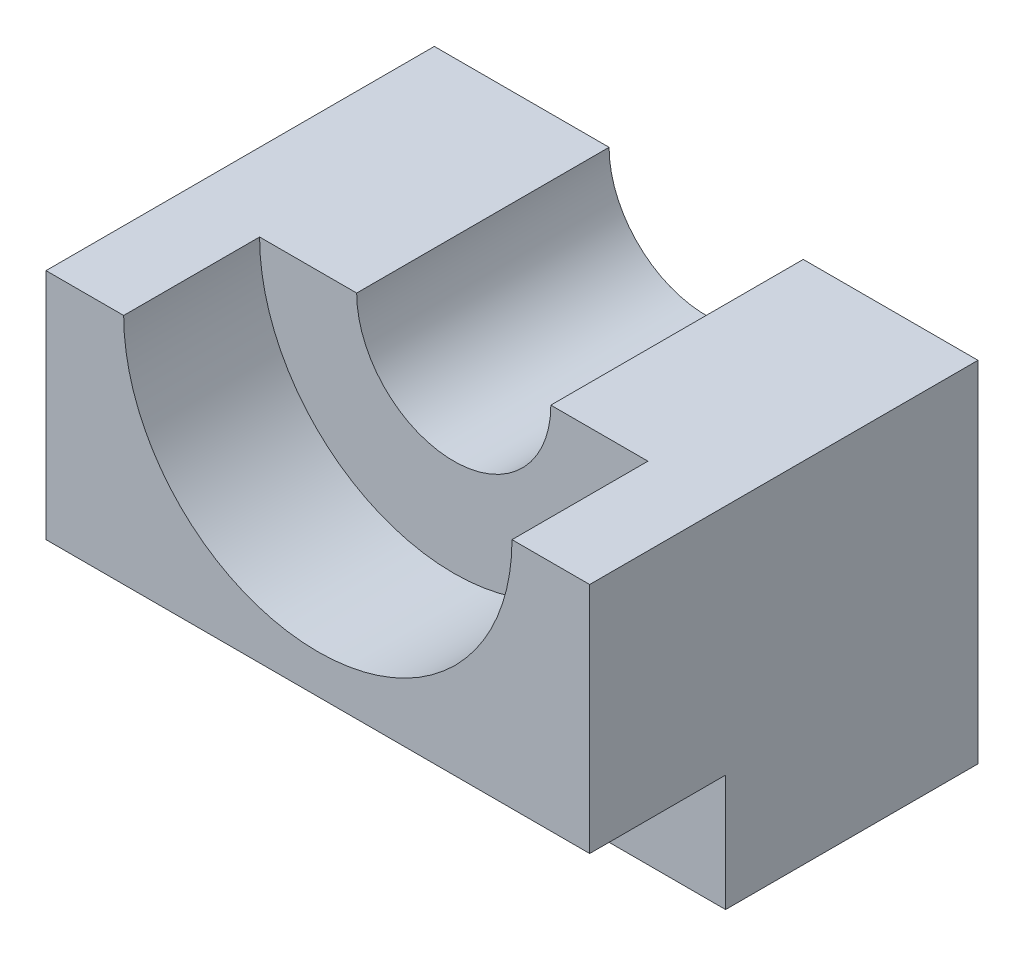
SolidWorks part; units mm, degrees
ref_plane "前视基准面" through (0, 0, 0) normal (0, 0, 1) x (1, 0, 0)
ref_plane "上视基准面" through (0, 0, 0) normal (0, 1, 0) x (1, 0, 0)
ref_plane "右视基准面" through (0, 0, 0) normal (1, 0, 0) x (0, 0, -1)
other "Configuration Table"
sketch "草图5" plane through (0, 0, 0) normal (0, 0, 1) x (1, 0, 0)
  line L0 (5, 9) -> (14, 9)
  line L1 (-14, -9) -> (14, -9)
  line L2 (-14, -9) -> (-14, 9)
  line L3 (-14, 9) -> (-5, 9)
  line L4 (14, -9) -> (14, 9)
  line L5 (-14, -9) -> (14, 9) construction
  line L6 (-14, 9) -> (14, -9) construction
  line L7 (-14, 1.6348) -> (14, 1.6348)
  line L8 (-14, 1.6348) -> (-14, 9)
  line L9 (-14, 9) -> (-5, 9)
  line L10 (14, 1.6348) -> (14, 9)
  line L11 (-14, 1.6348) -> (14, 9) construction
  line L12 (-14, 9) -> (14, 1.6348) construction
  line L13 (5, 9) -> (14, 9)
  arc A0 (-5, 9) -> (5, 9) centre (0, 9) ccw
  point P0 (0, 0)
  point P6 (0, 5.3174)
  dimension "D3" = 10
  dimension "D1" = 18
  dimension "D2" = 28
extrude "凸台-拉伸3" add sketch "草图5" along normal blind 13 contours A0 L3 L2 L7 L4 L0 region at (9.5, 8.7105, 0)
extrude "凸台-拉伸4" add sketch "草图5<4>" along normal blind 13 separate body contours L7 L2 L1 L4 region at (0, -3.6826, 0)
sketch "草图5<4>" plane through (0, 0, 0) normal (0, 0, 1) x (1, 0, 0) same geometry as "草图5"
sketch "草图6" plane through (0, 0, 13) normal (0, 0, 1) x (1, 0, 0)
  line L0 (-1008.012, 9) -> (48991.988, 9) construction
  line L2 (0, -1000) -> (0, 49000) construction
  line L4 (14, -9) -> (14, 1.6348) construction
  line L5 (-14, 9) -> (14, 9)
  line L6 (-14, 9) -> (-14, -3)
  line L7 (-14, -3) -> (14, -3)
  line L8 (14, 9) -> (14, -3)
  arc A0 (-10, 9) -> (10, 9) centre (0, 9) ccw
  line M8 (-14, 9) -> (-14, 1.6348)
  line M9 (-14, 1.6348) -> (14, 1.6348)
  line M10 (14, 1.6348) -> (14, 9)
  line M11 (14, 9) -> (5, 9)
  dimension "D1" = 10
  dimension "D2" = 12
extrude "凸台-拉伸5" add sketch "草图6" along normal blind 7 contours A0 M9 M10 M11 | A0 L6 L7 L8 M9 | A0 L5 M8 M9 region at (-11.4139, 4.9369, 13) region at (-10.3821, 1.351, 13) region at (11.4139, 4.9369, 13)
